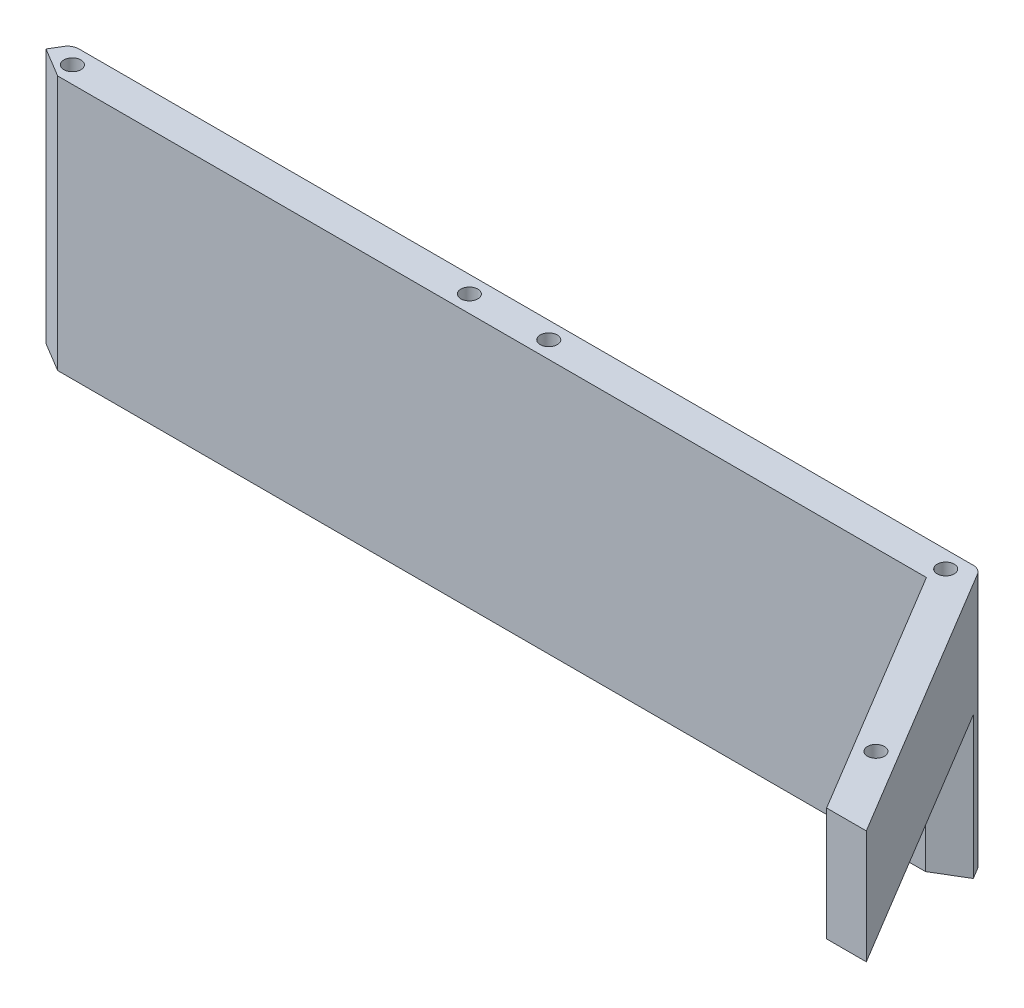
SolidWorks part; units mm, degrees
ref_plane "Front Plane" through (0, 0, 0) normal (0, 0, 1) x (1, 0, 0)
ref_plane "Top Plane" through (0, 0, 0) normal (0, 1, 0) x (1, 0, 0)
ref_plane "Right Plane" through (0, 0, 0) normal (1, 0, 0) x (0, 0, -1)
sketch "Sketch1" plane through (0, 0, 0) normal (0, 1, 0) x (1, 0, 0)
  line L0 (-110, 0) -> (-80, 50)
  line L1 (-80, 50) -> (80, 50)
  line L3 (76.6, 44) -> (-76.6, 44)
  line L4 (-76.6, 44) -> (-103, 0)
  line L5 (-103, 0) -> (-110, 0)
  line L6 (0, -55) -> (0, 55) construction
  line L7 (103, 0) -> (110, 0)
  line L8 (76.6, 44) -> (103, 0)
  line L9 (110, 0) -> (80, 50)
  dimension "D1" = 6
  dimension "D2" = 7
  dimension "D3" = 50
  dimension "D4" = 30
extrude "Boss-Extrude1" add sketch "Sketch1" along normal mid plane 45
sketch "Sketch2" plane through (0, 22.5, 0) normal (0, 1, 0) x (1, 0, 0)
  line L1 (-80, 50) -> (-110, 0) construction
  line L2 (80, 50) -> (-80, 50) construction
  line L3 (0, -55) -> (0, 55) construction
  circle A0 centre (-98.7014, 13) radius 1.5
  circle A1 centre (-77, 47) radius 1.5
  circle A2 centre (-7, 47) radius 1.5
  circle A3 centre (7, 47) radius 1.5
  circle A4 centre (77, 47) radius 1.5
  circle A5 centre (98.7014, 13) radius 1.5
  dimension "D2" = 3
  dimension "D3" = 3
  dimension "D5" = 3
  dimension "D1" = 70
  dimension "D4" = 7
  dimension "D6" = 3
  dimension "D7" = 3
  dimension "D8" = 3
  dimension "D9" = 37
extrude "Cut-Extrude1" cut sketch "Sketch2" against normal blind 5
fillet "Fillet1" radius 2 2 edges at (80, 0, -50) (-80, 0, -50)
sketch "Sketch4" plane through (80.8824, 0, -48.5294) normal (0.8575, 0, -0.5145) x (-0.5145, 0, -0.8575)
  line L0 (-56.5945, 22.5) -> (-56.5945, -22.5) construction
  line L1 (-56.5945, 2.5) -> (-1.5945, 2.5)
  line L2 (-56.5945, 2.5) -> (-56.5945, -22.5)
  line L3 (-56.5945, -22.5) -> (-1.5945, -22.5)
  line L4 (-1.5945, 2.5) -> (-1.5945, -22.5)
  line L5 (-56.5945, 22.5) -> (0.5826, 22.5) construction
  dimension "D1" = 55
  dimension "D2" = 25
  dimension "D3" = 20
extrude "Cut-Extrude3" cut sketch "Sketch4" against normal blind 10
sketch "Sketch5" plane through (-75.7353, 0, -45.4412) normal (0.8575, 0, 0.5145) x (0.5145, 0, -0.8575)
  line L0 (-56.5945, 22.5) -> (-56.5945, -22.5) construction
  line L1 (-56.5945, -17.5) -> (-51.5945, -17.5)
  line L2 (-56.5945, -17.5) -> (-56.5945, -22.5)
  line L3 (-56.5945, -22.5) -> (-51.5945, -22.5)
  line L4 (-51.5945, -17.5) -> (-51.5945, -22.5)
  line L5 (-52.9931, -22.5) -> (-1.6807, -22.5) construction
  dimension "D1" = 5
  dimension "D2" = 5
extrude "Cut-Extrude4" cut sketch "Sketch5" against normal blind 10
sketch "Sketch6" plane through (-75.7353, 0, -45.4412) normal (0.8575, 0, 0.5145) x (0.5145, 0, -0.8575)
  line L0 (-52.9931, 22.5) -> (-1.6807, 22.5) construction
  line L1 (-1.6807, -22.5) -> (-61.6807, -22.5)
  line L2 (-1.6807, -22.5) -> (-1.6807, 22.5)
  line L3 (-1.6807, 22.5) -> (-61.6807, 22.5)
  line L4 (-61.6807, -22.5) -> (-61.6807, 22.5)
  point P9 (-56.5945, 13.4331)
  point P10 (-56.5945, 13.4331)
  point P11 (-56.5945, 13.4331)
  point P12 (-56.5945, 13.4331)
  dimension "D1" = 0
  dimension "D2" = 60
extrude "Cut-Extrude5" cut sketch "Sketch6" against normal blind 10
